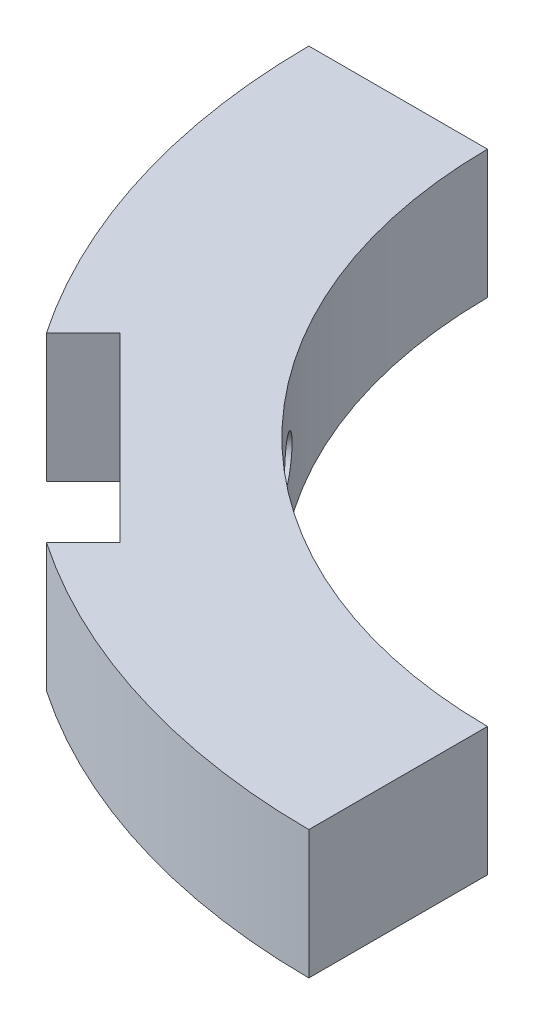
SolidWorks part; units mm, degrees
material "6061-T6 (SS)"
ref_plane "Front Plane" through (0, 0, 0) normal (0, 0, 1) x (1, 0, 0)
ref_plane "Top Plane" through (0, 0, 0) normal (0, 1, 0) x (1, 0, 0)
ref_plane "Right Plane" through (0, 0, 0) normal (1, 0, 0) x (0, 0, -1)
sketch "Sketch1" plane through (0, 0, 0) normal (0, 1, 0) x (1, 0, 0)
  line L0 (0, 0) -> (-24.5, 0) construction
  line L1 (0, 0) -> (0, -24.5) construction
  line L2 (-19.5497, -0.1) -> (-26.4998, -0.1)
  line L3 (-0.1, -19.5497) -> (-0.1, -26.4998)
  line L4 (-0.1, -0.1) -> (-24.5, -0.1) construction
  line L5 (-0.1, -0.1) -> (-0.1, -24.5) construction
  arc A0 (-19.5497, -0.1) -> (-0.1, -19.5497) centre (0, 0) ccw
  arc A1 (-26.4998, -0.1) -> (-0.1, -26.4998) centre (0, 0) ccw
  dimension "D1" = 39.1
  dimension "D2" = 53
  dimension "D3" = 0.1
extrude "Boss-Extrude1" add sketch "Sketch1" along normal mid plane 5
sketch "Sketch2" plane through (0, 2.5, 0) normal (0, 1, 0) x (1, 0, 0)
  line L0 (-18.7383, -18.7383) -> (0, 0) construction
  line L1 (-22.2739, -15.2028) -> (-15.2028, -22.2739)
  line L5 (-22.2739, -15.2028) -> (-20.5061, -13.435)
  line L6 (-20.5061, -13.435) -> (-13.435, -20.5061)
  line L7 (-13.435, -20.5061) -> (-15.2028, -22.2739)
  arc A0 (-26.4998, -0.1) -> (-0.1, -26.4998) centre (0, 0) ccw construction
  point P9 (-18.7383, -18.7383)
  dimension "D1" = 2.5
  dimension "D2" = 10
extrude "Cut-Extrude1" cut sketch "Sketch2" against normal through all
sketch "Sketch3" plane through (-16.9706, 0, 16.9706) normal (-0.7071, 0, 0.7071) x (0.7071, 0, 0.7071)
  line L0 (-5, 0) -> (5, 0) construction
  line L1 (-5, -2.5) -> (-5, 2.5) construction
  line L2 (5, 2.5) -> (5, -2.5) construction
  line L3 (0, 0) -> (0, 2.5) construction
  line L4 (5, 2.5) -> (-5, 2.5) construction
  point P6 (-2.5, 0)
  point P12 (2.5, 0)
  dimension "D1" = 2.5
hole_wizard "Tap Drill for M2x0.4 Tap1" positions "3DSketch1" profile "Sketch4" hole size "M2x0.4" standard "ANSI Metric" end condition through all
sketch3d "3DSketch1"
  point P0 (-18.7383, 0, 15.2028)
  point P3 (-15.2028, 0, 18.7383)
sketch "Sketch4" plane through (-18.7383, 0, 15.2028) normal (0, 1, 0) x (0.7071, 0, 0.7071)
  line L0 (0, 0) -> (0, 23.8586)
  line L1 (0, 23.8586) -> (0.8, 23.8586)
  line L2 (0.8, 23.8586) -> (0.8, 0)
  line L5 (0.8, 0) -> (0, 0)
  line L11 (0, -6.35) -> (0, 107.95) construction
  dimension "Thru Hole Dia." = 1.6
  dimension "Thru Hole Depth" = 23.8586
thread "Thread1" pitch 0.4 method extrude profile "Thread Profile1" start angle 0, offset 0, length 2.3, pitch 0.4, diameter 1.6
ref_plane "Plane1" through (-19.304, 0, 14.6371) normal (0, -1, 0) x (-0.7071, 0, -0.7071)
sketch "Thread Profile1" plane through (-19.304, 0, 14.6371) normal (0, -1, 0) x (-0.7071, 0, -0.7071)
  line L0 (0, 0) -> (0, 0.4) construction
  line L11 (0, 0) -> (0, 0.35)
  line L12 (0, 0.35) -> (-0.2165, 0.225)
  line L13 (-0.2165, 0.225) -> (-0.2165, 0.125)
  line L15 (-0.2165, 0.125) -> (0, 0)
  line L17 (-0.2165, 0.175) -> (0, 0.175) construction
  point P2 (0, 0)
  dimension "Pitch" = 0.4
  dimension "Profile_Angle" = 60
  dimension "Profile_Land" = 0.1
  dimension "Profile_Height" = 0.2165
thread "Thread2" pitch 0.4 method extrude profile "Thread Profile2" start angle 0, offset 0, length 2.3, pitch 0.4, diameter 1.6
ref_plane "Plane2" through (-15.7685, 0, 18.1726) normal (0, -1, 0) x (-0.7071, 0, -0.7071)
sketch "Thread Profile2" plane through (-15.7685, 0, 18.1726) normal (0, -1, 0) x (-0.7071, 0, -0.7071)
  line L0 (0, 0) -> (0, 0.4) construction
  line L11 (0, 0) -> (0, 0.35)
  line L12 (0, 0.35) -> (-0.2165, 0.225)
  line L13 (-0.2165, 0.225) -> (-0.2165, 0.125)
  line L15 (-0.2165, 0.125) -> (0, 0)
  line L17 (-0.2165, 0.175) -> (0, 0.175) construction
  point P2 (0, 0)
  dimension "Pitch" = 0.4
  dimension "Profile_Angle" = 60
  dimension "Profile_Land" = 0.1
  dimension "Profile_Height" = 0.2165
